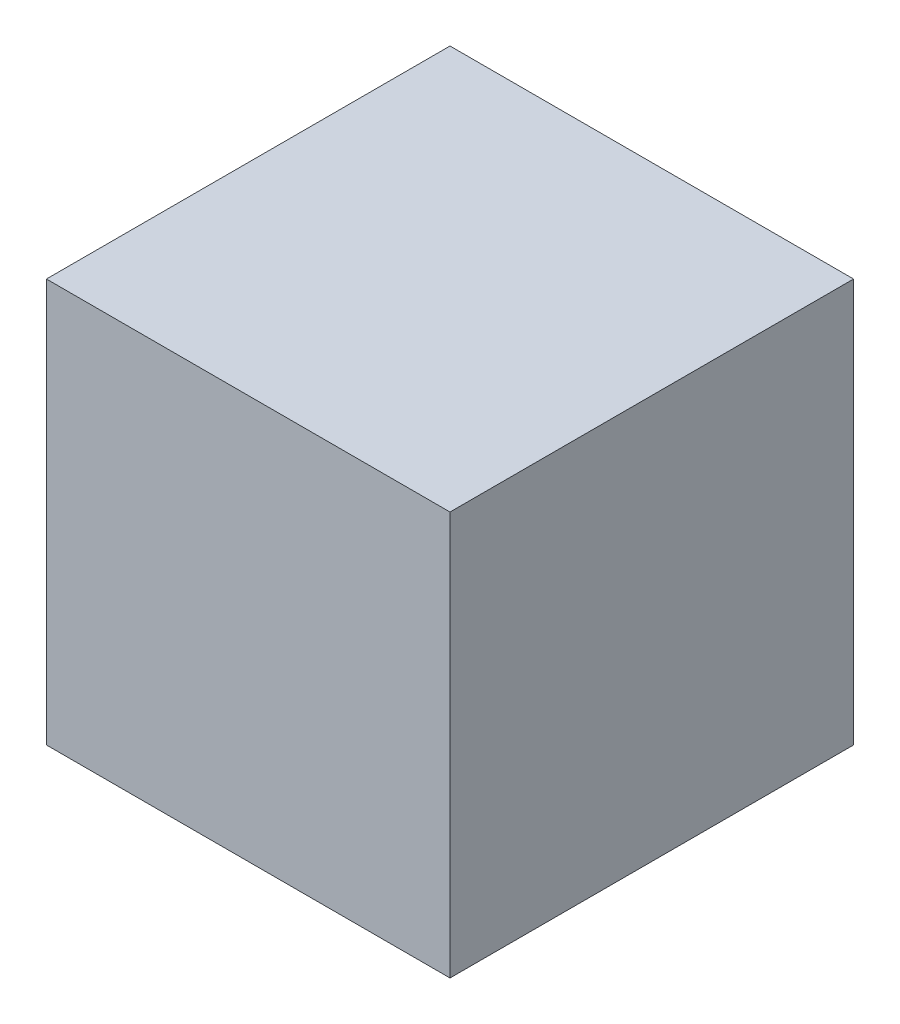
SolidWorks part; units mm, degrees
ref_plane "Front Plane" through (0, 0, 0) normal (0, 0, 1) x (1, 0, 0)
ref_plane "Top Plane" through (0, 0, 0) normal (0, 1, 0) x (1, 0, 0)
ref_plane "Right Plane" through (0, 0, 0) normal (1, 0, 0) x (0, 0, -1)
sketch "Sketch1" plane through (0, 0, 0) normal (0, 1, 0) x (1, 0, 0)
  line L1 (30, -30) -> (-30, -30)
  line L2 (30, -30) -> (30, 30)
  line L3 (30, 30) -> (-30, 30)
  line L4 (-30, -30) -> (-30, 30)
  line L5 (30, -30) -> (-30, 30) construction
  line L6 (30, 30) -> (-30, -30) construction
  point P1 (0, 0)
  dimension "D1" = 60
  dimension "D2" = 60
extrude "Boss-Extrude1" add sketch "Sketch1" along normal blind 60
sketch "Sketch2" plane through (0, 0, 0) normal (0, -1, 0) x (1, 0, 0)
  line L1 (27.5, -27.5) -> (-27.5, -27.5)
  line L2 (27.5, -27.5) -> (27.5, 27.5)
  line L3 (27.5, 27.5) -> (-27.5, 27.5)
  line L4 (-27.5, -27.5) -> (-27.5, 27.5)
  line L5 (27.5, -27.5) -> (-27.5, 27.5) construction
  line L6 (27.5, 27.5) -> (-27.5, -27.5) construction
  point P0 (0, 0)
  dimension "D1" = 55
  dimension "D2" = 55
extrude "Boss-Extrude2" add sketch "Sketch2" against normal blind 57.5
extrude "Cut-Extrude1" cut sketch "Sketch2<2>" against normal blind 57.5
sketch "Sketch2<2>" plane through (0, 0, 0) normal (0, -1, 0) x (1, 0, 0) same geometry as "Sketch2"
sketch "Sketch5" plane through (0, 0, -30) normal (0, 0, -1) x (-1, 0, 0)
  line L0 (30, 60) -> (30, 0) construction
  line L1 (25, 5) -> (-25, 5)
  line L2 (25, 5) -> (25, 55)
  line L3 (25, 55) -> (-25, 55)
  line L4 (-25, 5) -> (-25, 55)
  line L5 (25, 5) -> (-25, 55) construction
  line L6 (25, 55) -> (-25, 5) construction
  line L7 (-30, 60) -> (30, 60) construction
  point P0 (0, 30)
  dimension "D1" = 50
  dimension "D2" = 50
  dimension "D3" = 30
  dimension "D4" = 30
extrude "Cut-Extrude2" cut sketch "Sketch5" against normal blind 20
sketch "Sketch6" plane through (0, 0, -30) normal (0, 0, -1) x (-1, 0, 0)
  line L0 (30, 60) -> (30, 0) construction
  line L1 (15, 1.25) -> (-15, 1.25)
  line L2 (15, 1.25) -> (15, 4.75)
  line L3 (15, 4.75) -> (-15, 4.75)
  line L4 (-15, 1.25) -> (-15, 4.75)
  line L5 (15, 1.25) -> (-15, 4.75) construction
  line L6 (15, 4.75) -> (-15, 1.25) construction
  line L7 (-30, 0) -> (30, 0) construction
  point P0 (0, 3)
  point P5 (0, 0)
  point P8 (0, 0)
  dimension "D1" = 3.5
  dimension "D2" = 30
  dimension "D3" = 30
  dimension "D4" = 3
extrude "Cut-Extrude3" cut sketch "Sketch6" against normal blind 20
sketch "Sketch7" plane through (0, 0, -30) normal (0, 0, -1) x (-1, 0, 0)
  line L0 (30, 60) -> (30, 0) construction
  line L2 (-30, 0) -> (30, 0) construction
  circle A0 centre (10, 0.6) radius 0.5
  point P6 (9.8877, 0.5723)
  dimension "D1" = 1
  dimension "D2" = 20
  dimension "D3" = 0.6
extrude "Cut-Extrude4" cut sketch "Sketch7" against normal blind 3.3
ref_plane "Plane1" through (0, 0, 0) normal (-1, 0, 0) x (0, 0, 1)
mirror "Mirror1" about plane through (0, 0, 0) normal (-1, 0, 0) of "Cut-Extrude4"
